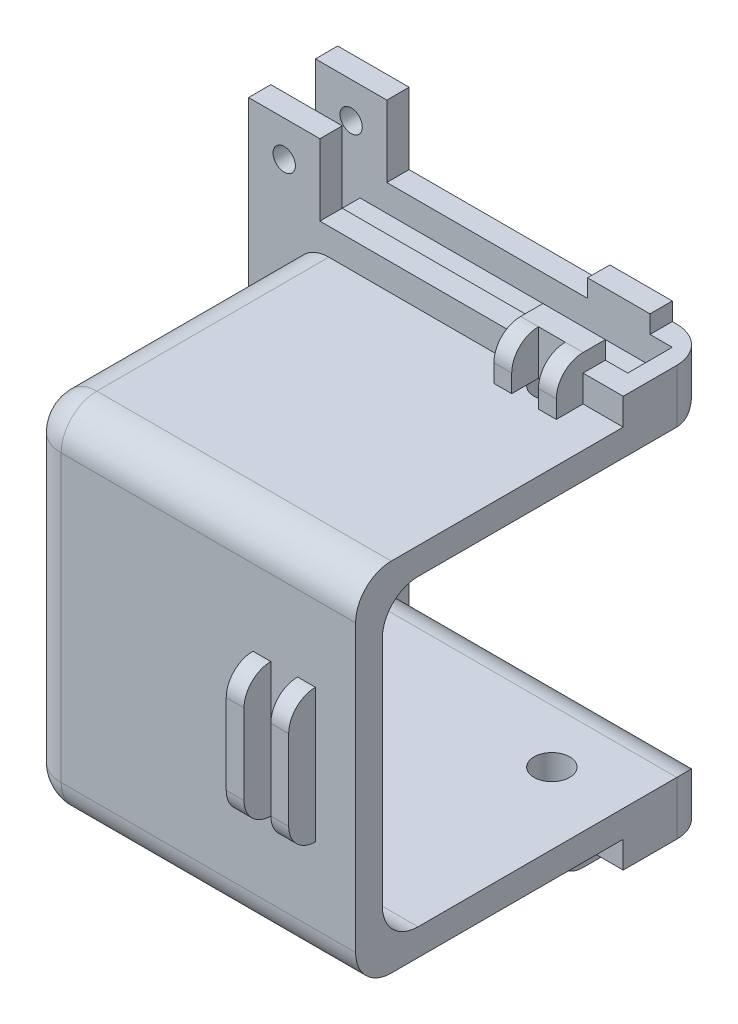
SolidWorks part; units mm, degrees
material "PVC rigido"
ref_plane "Piano frontale" through (0, 0, 0) normal (0, 0, 1) x (1, 0, 0)
ref_plane "Piano superiore" through (0, 0, 0) normal (0, 1, 0) x (1, 0, 0)
ref_plane "Piano destro" through (0, 0, 0) normal (1, 0, 0) x (0, 0, -1)
sketch "Schizzo1" plane through (0, 0, 0) normal (0, 0, 1) x (1, 0, 0)
  line L0 (8, 0) -> (0, 0) construction
  line L1 (0, -23) -> (42, -23)
  line L2 (0, -23) -> (0, 23)
  line L3 (0, 23) -> (42, 23)
  line L4 (42, 23) -> (42, 17)
  line L5 (8, -17) -> (42, -17)
  line L6 (8, -17) -> (8, 17)
  line L7 (8, 17) -> (42, 17)
  line L8 (42, -17) -> (42, -23)
  line L10 (8, 17) -> (8, 20) construction
  line L11 (5, 20) -> (40, 20) construction
  dimension "D1" = 6
  dimension "D2" = 42
  dimension "D3" = 3
  dimension "D4" = 8
extrude "Estrusione-Estrusione1" add sketch "Schizzo1" along normal blind 10 contours L2 L3 L4 L7 L6 L5 L8 L1
sketch "Schizzo6" plane through (0, 0, 10) normal (0, 0, 1) x (1, 0, 0)
  line L0 (8, -17) -> (8, 17) construction
  line L1 (0, -23) -> (8, -23)
  line L2 (0, -23) -> (0, -31)
  line L3 (0, -31) -> (8, -31)
  line L4 (8, -23) -> (8, -31)
  line L5 (0, 23) -> (8, 23)
  line L6 (0, 23) -> (0, 31)
  line L7 (0, 31) -> (8, 31)
  line L8 (8, 23) -> (8, 31)
  line L10 (37.5, -23) -> (30.5, -23)
  line L11 (37.5, -23) -> (37.5, -25)
  line L12 (37.5, -25) -> (30.5, -25)
  line L13 (30.5, -23) -> (30.5, -25)
  line L14 (37.5, 23) -> (30.5, 23)
  line L15 (37.5, 23) -> (37.5, 25)
  line L16 (37.5, 25) -> (30.5, 25)
  line L17 (30.5, 23) -> (30.5, 25)
  line L18 (0, -23) -> (42, -23) construction
  line L19 (0, 23) -> (42, 23) construction
  line L20 (34, -25) -> (34, -23) construction
  line L21 (42, -17) -> (42, -23) construction
  dimension "D1" = 7
  dimension "D2" = 8
  dimension "D3" = 50
extrude "Estrusione-Estrusione4" add sketch "Schizzo6" against normal up to surface (10 mm away) up to face at (23, 0, 0)
sketch "Schizzo2" plane through (42, 0, 0) normal (1, 0, 0) x (0, 0, -1)
  line L0 (-10, -23) -> (0, -23) construction
  line L1 (-7.5, -23) -> (-7.5, -41.8171)
  line L2 (-7.5, -23) -> (-7.5, -20)
  line L3 (-7.5, -20) -> (-2.5, -20)
  line L4 (-2.5, -22.5) -> (-2.5, -20)
  line L5 (-5, -20) -> (-5, -17) construction
  line L6 (-10, -17) -> (0, -17) construction
  line L7 (-7.5, -41.8171) -> (-2.5, -41.8171)
  line L8 (-2.5, -41.8171) -> (-2.5, -22.5)
  dimension "D1" = 3
  dimension "D2" = 5
extrude "Taglio-Estrusione1" cut sketch "Schizzo2" against normal through all
sketch "Schizzo4" plane through (0, -20, 0) normal (0, -1, 0) x (-1, 0, 0)
  line L0 (0, -7.5) -> (-42, -7.5) construction
  line L1 (-42, -2.5) -> (-40, -2.5)
  line L2 (-42, -2.5) -> (-42, -7.5)
  line L3 (-42, -7.5) -> (-40, -7.5)
  line L4 (-40, -2.5) -> (-40, -7.5)
  line L5 (-40, -7.5) -> (-40, -2.5) construction
extrude "Estrusione-Estrusione2" add sketch "Schizzo4" along normal up to surface (3 mm away) up to face at (39.1875, -23, 1.25)
mirror "Specchia1" about plane through (0, 0, 0) normal (0, 1, 0) of "Taglio-Estrusione1"
sketch "Schizzo5" plane through (0, 20, 0) normal (0, 1, 0) x (1, 0, 0)
  line L0 (0, -2.5) -> (42, -2.5) construction
  line L1 (42, -2.5) -> (40, -2.5)
  line L2 (42, -2.5) -> (42, -7.5)
  line L3 (42, -7.5) -> (40, -7.5)
  line L4 (40, -2.5) -> (40, -7.5)
  line L5 (42, -2.5) -> (42, -7.5) construction
  line L6 (0, -7.5) -> (42, -7.5) construction
  line L7 (40, -2.5) -> (40, -7.5) construction
extrude "Estrusione-Estrusione3" add sketch "Schizzo5" along normal up to surface (3 mm away) up to face at (39.1875, 23, 8.75)
sketch "Schizzo3" plane through (0, -20, 0) normal (0, -1, 0) x (1, 0, 0)
  line L0 (0, 7.5) -> (40, 7.5) construction
  line L1 (0, 2.5) -> (5, 2.5)
  line L2 (0, 2.5) -> (0, 7.5)
  line L3 (0, 7.5) -> (5, 7.5)
  line L4 (5, 2.5) -> (5, 7.5)
  dimension "D1" = 5
extrude "Taglio-Estrusione2" cut sketch "Schizzo3" against normal through all
hole_wizard "Foro filettato M3x0.5-1" positions "Schizzo8" profile "Schizzo7" tap size "M3x0.5" standard "Ansi Metric" end condition through all
sketch "Schizzo8" plane through (0, 0, 10) normal (0, 0, 1) x (1, 0, 0)
  line L0 (8, -27) -> (4, -27) construction
  line L1 (8, -31) -> (8, -23) construction
  line L2 (4, -27) -> (4, -31) construction
  line L3 (0, -31) -> (8, -31) construction
  line L5 (8, 27) -> (4, 27) construction
  line L6 (8, 23) -> (8, 31) construction
  line L7 (4, 27) -> (4, 31) construction
  line L8 (8, 31) -> (0, 31) construction
  point P0 (4, -27)
  point P2 (4, 27)
sketch "Schizzo7" plane through (4, -27, 10) normal (1, 0, 0) x (0, -1, 0)
  line L0 (0, 0) -> (0, 10)
  line L1 (0, 10) -> (1.25, 10)
  line L2 (1.25, 10) -> (1.25, 0)
  line L5 (1.25, 0) -> (0, 0)
  line L11 (0, -6.35) -> (0, 107.95) construction
  dimension "Thru Tap Drill Dia." = 2.5
  dimension "Thru Tap Drill Depth" = 10
cosmetic thread "Filettatura del foro1" parameters "D2"=3
cosmetic thread "Filettatura del foro2" parameters "D2"=3
sketch "Schizzo9" plane through (0, 0, 10) normal (0, 0, 1) x (1, 0, 0)
  line L0 (42, 23) -> (42, 17) construction
  line L1 (5, -20) -> (42, -20)
  line L2 (5, -20) -> (5, 20)
  line L3 (5, 20) -> (42, 20)
  line L4 (42, -20) -> (42, -17)
  line L5 (42, -17) -> (8, -17)
  line L6 (8, -17) -> (8, 17)
  line L7 (8, -17) -> (8, 17) construction
  line L8 (8, 17) -> (42, 17)
  line L9 (42, 17) -> (42, 20)
  line L10 (42, -17) -> (42, -23) construction
  line L11 (5, 0) -> (8, 0) construction
extrude "Estrusione-Estrusione5" add sketch "Schizzo9" along normal blind 30
sketch "Schizzo10" plane through (8, 0, 0) normal (1, 0, 0) x (0, 0, -1)
  line L0 (-40, 17) -> (0, 17) construction
  line L1 (-40, -17) -> (-37, -17)
  line L2 (-40, -17) -> (-40, 17)
  line L3 (-40, 17) -> (-37, 17)
  line L4 (-37, -17) -> (-37, 17)
  line L5 (-40, -20) -> (-40, -17) construction
extrude "Estrusione-Estrusione6" add sketch "Schizzo10" along normal up to surface (34 mm away) up to face at (42, -19.75, 19.1667)
sketch "Schizzo14" plane through (0, -20, 0) normal (0, -1, 0) x (1, 0, 0)
  line L0 (34, 10) -> (42, 10) construction
  line L1 (42, 40) -> (42, 10) construction
  line L2 (34, 10) -> (34, 40) construction
  line L5 (5, 40) -> (42, 40) construction
  circle A0 centre (34, 10) radius 2
  dimension "D1" = 8
  dimension "D3" = 4
  dimension "D2" = 30
extrude "Taglio-Estrusione3" cut sketch "Schizzo14" against normal up to surface (40 mm away) up to face at (28.125, 20, 28.75)
sketch "Schizzo11" plane through (0, 0, 40) normal (0, 0, 1) x (1, 0, 0)
  line L0 (42, 0) -> (37.5, 0) construction
  line L1 (37.5, -7.5) -> (35.5, -7.5)
  line L2 (37.5, -7.5) -> (37.5, 7.5)
  line L3 (37.5, 7.5) -> (35.5, 7.5)
  line L4 (35.5, -7.5) -> (35.5, 7.5)
  line L5 (30.5, -7.5) -> (32.5, -7.5)
  line L6 (30.5, -7.5) -> (30.5, 7.5)
  line L7 (30.5, 7.5) -> (32.5, 7.5)
  line L8 (32.5, -7.5) -> (32.5, 7.5)
  line L9 (42, -20) -> (42, 20) construction
  line L10 (37.5, 0) -> (35.5, 0) construction
  line L11 (35.5, 0) -> (32.5, 0) construction
  line L12 (32.5, 0) -> (30.5, 0) construction
  dimension "D1" = 2
  dimension "D2" = 15
  dimension "D3" = 3
  dimension "D4" = 11.5
extrude "Estrusione-Estrusione7" add sketch "Schizzo11" along normal blind 3
sketch "Schizzo12" plane through (0, 0, 10) normal (0, 0, 1) x (1, 0, 0)
  line L0 (36, -20) -> (42, -20) construction
  line L1 (37.5, -25) -> (35.5, -25)
  line L2 (37.5, -25) -> (37.5, -20)
  line L3 (37.5, -20) -> (35.5, -20)
  line L4 (35.5, -25) -> (35.5, -20)
  line L5 (32.5, -7.5) -> (32.5, 7.5) construction
  line L6 (30.5, -25) -> (32.5, -25)
  line L7 (30.5, -25) -> (30.5, -20)
  line L8 (30.5, -20) -> (32.5, -20)
  line L9 (32.5, -25) -> (32.5, -20)
  line L10 (35.5, 7.5) -> (35.5, -7.5) construction
extrude "Estrusione-Estrusione8" add sketch "Schizzo12" along normal blind 3
mirror "Specchia2" about plane through (0, 0, 0) normal (0, 1, 0) of "Estrusione-Estrusione8"
fillet "Raccordo1" radius 4 11 edges at (23.5, -20, 40) (23.5, 20, 40) (5, 0, 40) (5, 20, 25) (5, -20, 25) (42, 20, 0) (42, -20, 0) (25, -17, 0) (25, 17, 0) (25, 17, 37) (25, -17, 37)
fillet "Raccordo2" radius 3 8 edges at (31.5, 25, 13) (36.5, 25, 13) (36.5, 7.5, 43) (31.5, 7.5, 43) (31.5, -7.5, 43) (36.5, -7.5, 43) (31.5, -25, 13) (36.5, -25, 13)
